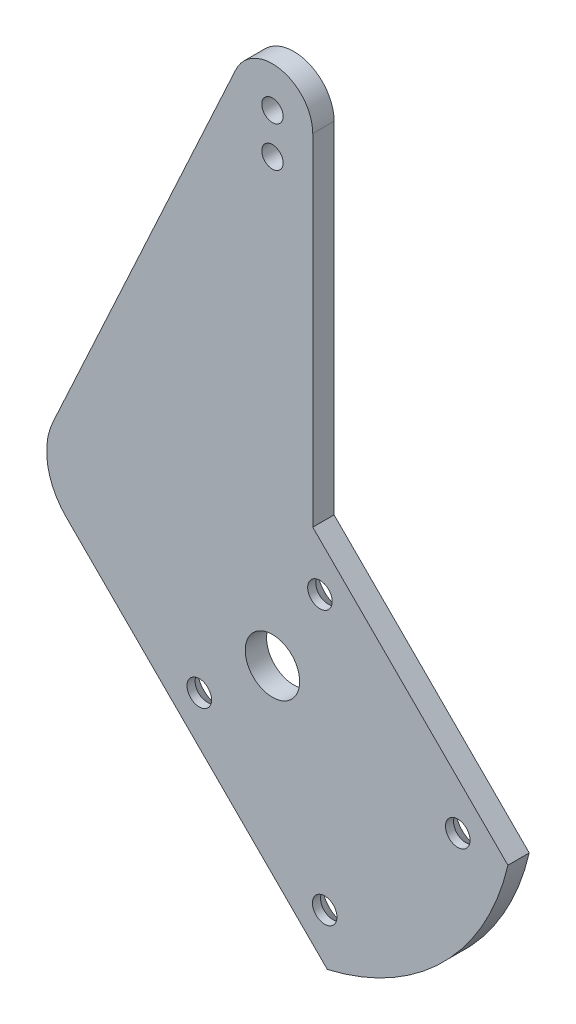
SolidWorks part; units mm, degrees
material "6061-T6 (SS)"
ref_plane "Front" through (0, 0, 0) normal (0, 0, 1) x (1, 0, 0)
ref_plane "Top" through (0, 0, 0) normal (0, 1, 0) x (1, 0, 0)
ref_plane "Right" through (0, 0, 0) normal (1, 0, 0) x (0, 0, -1)
ref_axis "side-side" through (80.9, 0, 0) along (-1, 0, 0)
ref_axis "up-down" through (0, 50, 0) along (0, -1, 0)
ref_axis "front-back" through (0, 0, -80.9) along (0, 0, 1)
sketch "Sketch2" plane through (0, 0, 0) normal (0, 0, 1) x (1, 0, 0)
  line L0 (8.1701, -35.0401) -> (-22.5197, -4.3504) construction
  line L1 (4.3504, 22.5197) -> (35.0401, -8.1701) construction
  line L2 (8.1701, -35.0401) -> (-35.0401, 8.1701)
  line L3 (6, 20.8701) -> (35.0401, -8.1701)
  line L8 (-5.4487, 74.1114) -> (-32.674, 15.0656)
  line L9 (0, 0) -> (-58.6505, 41.0675) construction
  line L10 (6, 71.5991) -> (6, 20.8701)
  line L11 (0, 0) -> (0, 71.5991) construction
  arc A0 (8.1701, -35.0401) -> (35.0401, -8.1701) centre (0, 0) ccw construction
  arc A1 (8.1701, -35.0401) -> (35.0401, -8.1701) centre (0, 0) ccw
  circle A2 centre (0, 71.5991) radius 1.5875
  circle A3 centre (0, 65.5991) radius 1.5875
  circle A8 centre (0, 0) radius 4.05 construction
  circle A9 centre (0, 0) radius 4.05
  arc A11 (-5.4487, 74.1114) -> (6, 71.5991) centre (0, 71.5991) cw
  arc A12 (-35.0401, 8.1701) -> (-32.674, 15.0656) centre (0, 0) cw
  point P3 (7.0711, 12.7279)
  point P7 (-10.8866, -8.9124)
  point P9 (27.5772, -7.7782)
  dimension "D3" = 6
  dimension "D4" = 3.175
  dimension "D2" = 6
extrude "Boss-Extrude1" add sketch "Sketch2" against normal blind 3.175
hole_wizard "CSK for #6 Flat Head Machine Screw1" positions "Sketch3" profile "Sketch4" countersink size "#6" standard "ANSI Inch"
sketch "Sketch3" plane through (0, 0, -3.175) normal (0, 0, -1) x (-1, 0, 0)
  line L0 (0, 0) -> (-36.0579, -36.0579) construction
  line L2 (-6, 20.8701) -> (-35.0401, -8.1701) construction
  point P0 (-7.0711, 12.7279)
  point P2 (-27.5772, -7.7782)
  point P4 (10.8866, -8.9124)
  point P6 (-7.7782, -27.5772)
sketch "Sketch4" plane through (7.0711, 12.7279, -3.175) normal (1, 0, 0) x (0, 1, 0)
  line L0 (0, 0) -> (0, 12.0719)
  line L1 (0, 12.0719) -> (1.8288, 10.973)
  line L2 (1.8288, 10.973) -> (1.8288, 1.9723)
  line L3 (1.8288, 1.9723) -> (3.5433, 0)
  line L5 (3.5433, 0) -> (0, 0)
  line L6 (-1.8288, 1.9723) -> (-3.5433, 0) construction
  line L10 (0, 12.0719) -> (-1.8288, 10.973) construction
  line L11 (0, -6.35) -> (0, 107.95) construction
  dimension "Hole Dia." = 3.6576
  dimension "Hole Depth" = 10.973
  dimension "Near C'Sink Dia." = 7.0866
  dimension "Near C'Sink Angle" = 82
  dimension "Drill Angle" = 118
fillet "Fillet1" radius 10 1 edges at (-35.0401, 8.1701, -1.5875)
